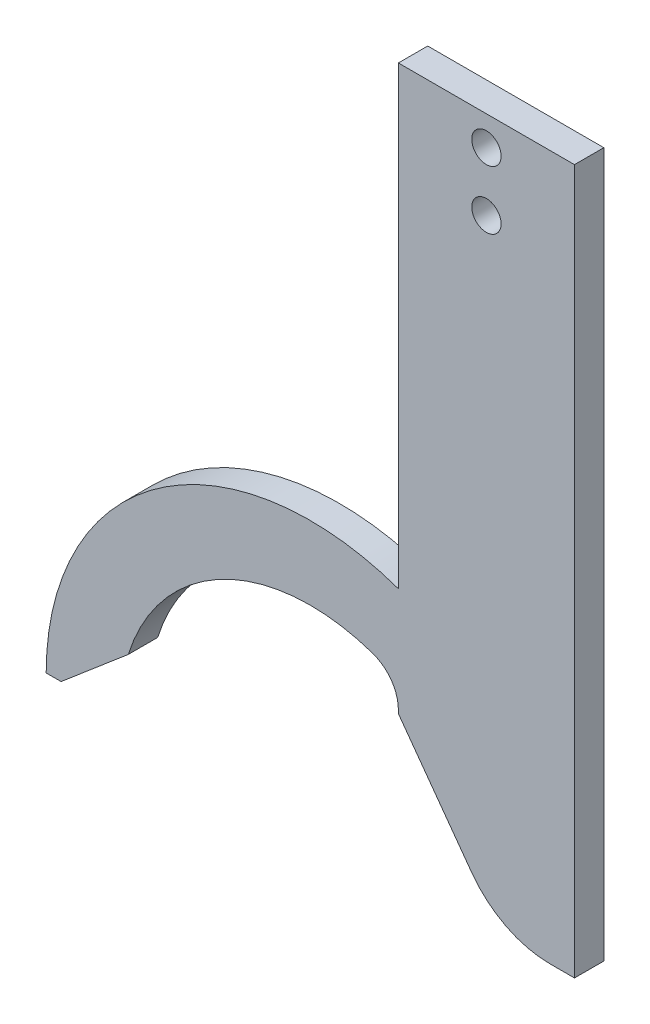
SolidWorks part; units mm, degrees
material "6063-T1"
ref_plane "Front Plane" through (0, 0, 0) normal (0, 0, 1) x (1, 0, 0)
ref_plane "Top Plane" through (0, 0, 0) normal (0, 1, 0) x (1, 0, 0)
ref_plane "Right Plane" through (0, 0, 0) normal (1, 0, 0) x (0, 0, -1)
sketch "Sketch1" plane through (0, 0, 0) normal (0, 0, 1) x (1, 0, 0)
  line L0 (0, 76.2) -> (0, -76.2) construction
  line L1 (-19.05, 76.2) -> (19.05, 76.2)
  line L2 (-19.05, 76.2) -> (-19.05, -76.2)
  line L3 (-19.05, -76.2) -> (19.05, -76.2)
  line L4 (19.05, 76.2) -> (19.05, -76.2)
  line L5 (-19.05, 76.2) -> (19.05, -76.2) construction
  line L6 (-19.05, -76.2) -> (19.05, 76.2) construction
  line L7 (-95.25, -76.2) -> (19.05, -76.2) construction
  line L8 (-95.25, -76.2) -> (-79.375, -76.2)
  line L10 (19.05, -14.7451) -> (19.05, -143.545) construction
  circle A0 centre (-38.1, -76.2) radius 57.15
  circle A1 centre (-38.1, -76.2) radius 41.275
  point P0 (0, 0)
  point P11 (-38.1, -56.9696)
  point P15 (-38.1, -65.7995)
  point P16 (0, 0)
  point P17 (0, 0)
  dimension "D3" = 114.3
  dimension "D4" = 82.55
  dimension "D1" = 38.1
  dimension "D2" = 152.4
extrude "Boss-Extrude1" add sketch "Sketch1" along normal blind 6.35 contours A0 L4 L1 L2 | A1 L3 A0 L2 | A1 L2 A0 L8 | L3 A1 L2 region at (1.1354, 18.984, 0) region at (0.9438, -50.1218, 0) region at (-61.364, -41.3077, 0) region at (-9.9164, -61.7943, 0)
fillet "Fillet1" radius 8.255 1 edges at (-19.05, -39.5841, 3.175)
chamfer "Chamfer1" distance 15.24 angle 48 1 edges at (-79.375, -76.2, 3.175) first distance on face at (-87.3125, -76.2, 3.175)
fillet "Fillet3" [suppressed] radius 20.955
sketch "Sketch2" plane through (0, 0, 6.35) normal (0, 0, 1) x (1, 0, 0)
  line L2 (19.05, 76.2) -> (19.05, -76.2) construction
  line L3 (-19.05, 76.2) -> (19.05, 76.2) construction
  circle A0 centre (0, 57.15) radius 3.175
  circle A1 centre (0, 69.85) radius 3.175
  point P4 (0, 5.4309)
  point P5 (0, 56.2107)
  point P6 (-0.159, -57.15)
  point P8 (0, -57.2235)
  point P9 (0, 0)
  dimension "D3" = 6.35
  dimension "D4" = 6.35
  dimension "D1" = 6.35
  dimension "D2" = 12.7
  dimension "D5" = 19.05
extrude "Cut-Extrude1" cut sketch "Sketch2" against normal through all
chamfer "Chamfer2" distance 30.48 angle 36 1 edges at (-19.05, -76.2, 3.175) first distance on face at (-19.05, -60.5972, 3.175)
fillet "Fillet4" radius 20.955 1 edges at (3.095, -76.2, 3.175)
